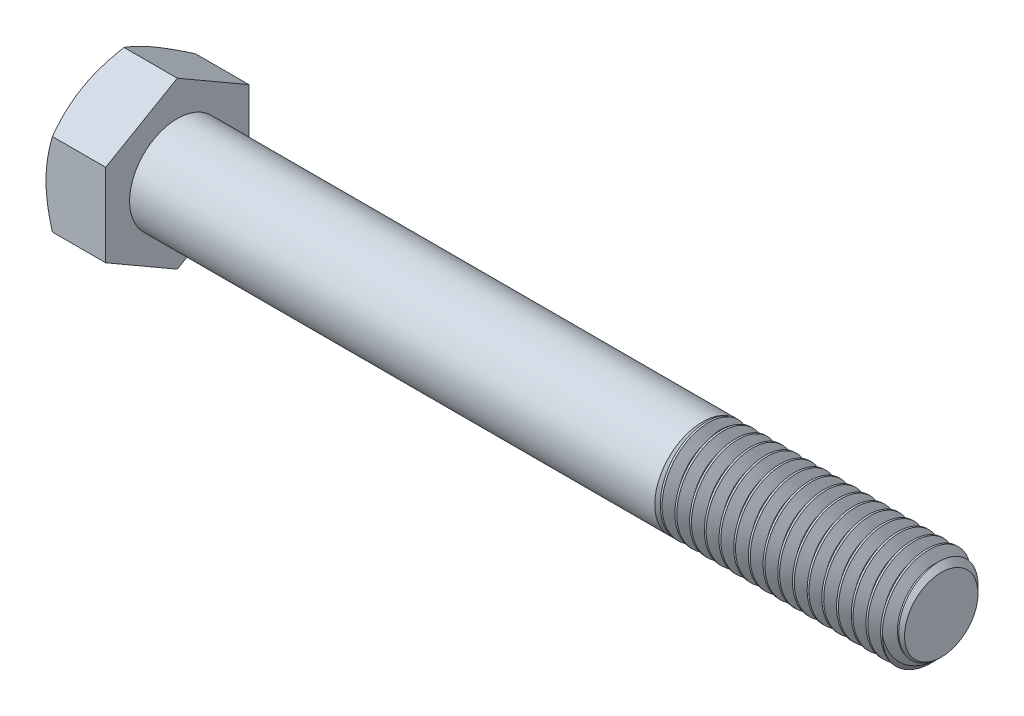
SolidWorks part; units mm, degrees
material "Plain Carbon Steel"
ref_plane "Front Plane" through (0, 0, 0) normal (0, 0, 1) x (1, 0, 0)
ref_plane "Top Plane" through (0, 0, 0) normal (0, 1, 0) x (1, 0, 0)
ref_plane "Right Plane" through (0, 0, 0) normal (1, 0, 0) x (0, 0, -1)
sketch "Sketch1" plane through (0, 0, 0) normal (0, 0, 1) x (1, 0, 0)
  line L0 (-54.7687, 0) -> (54.7687, 0) construction
  line L1 (54.7687, 6.35) -> (54.7687, -6.35) construction
  line L2 (-46.8312, 9.525) -> (-46.8312, -9.525) construction
  line L3 (-54.7687, 9.525) -> (-54.7687, -9.525) construction
  point P9 (-46.8312, 0)
  point P10 (47.9303, -6.35)
  dimension "Screw Dia" = 12.7
  dimension "Hex" = 19.05
  dimension "Head Ht" = 7.9375
  dimension "Screw Lenght" = 101.6
  dimension "D1" = 6.8385
ref_plane "Plane2" through (54.7687, 0, 0) normal (1, 0, 0) x (0, 0, -1)
sketch "Sketch5" plane through (54.7687, 0, 0) normal (1, 0, 0) x (0, 0, -1)
  circle A0 centre (0, 0) radius 6.35
extrude "Boss-Extrude3" add sketch "Sketch5" against normal up to vertex (101.6 mm away) up to point (-46.8312, 0, 0)
sketch "Sketch9" plane through (54.7687, 0, 0) normal (1, 0, 0) x (0, 0, -1)
  circle A1 centre (0, 0) radius 6.35
  circle A2 centre (0, 0) radius 6.35
  dimension "D1" = 0
curve "Helix/Spiral1" pitch 1.9538 height 33.7038 turns 17.25 parameters "Pitch"=1.9538
chamfer "Chamfer1" distance 1.4654 angle 45 1 edges at (54.7687, 0, -6.35)
sketch "Sketch10" plane through (0, 0, 0) normal (0, 0, 1) x (1, 0, 0)
  line L0 (54.7687, 6.35) -> (55.5014, 5.0809)
  line L1 (55.5014, 5.0809) -> (55.7457, 5.0809)
  line L2 (55.7457, 5.0809) -> (56.4784, 6.35)
  line L3 (54.7687, 6.35) -> (56.4784, 6.35)
  line L4 (55.6236, 6.35) -> (55.6236, 5.0809) construction
  line L5 (55.1351, 5.7155) -> (56.112, 5.7155) construction
  dimension "D1" = 60
  dimension "D2" = 0.2442
  dimension "D3" = 0.9769
sweep "Cut-Sweep1" cut profiles "Sketch10" path "Helix/Spiral1" align with end faces yes
sketch "Sketch11" plane through (0, 0, 0) normal (0, 0, 1) x (1, 0, 0)
  line L0 (-46.8312, 6.35) -> (-46.8312, 0)
  line L1 (-46.8312, 0) -> (29.3688, 0)
  line L3 (29.3688, 0) -> (23.0187, 6.35)
  line L4 (-46.8312, 6.35) -> (23.0187, 6.35)
  dimension "D1" = 45
  dimension "MIn Thread" = 31.75
revolve "Revolve1" add sketch "Sketch11" angle 360 about L1
sketch "Sketch6" plane through (-46.8312, 0, 0) normal (-1, 0, 0) x (0, 0, 1)
  line L0 (0, 9.525) -> (0, -9.525) construction
  line L1 (9.525, 5.4993) -> (0, 10.9985)
  line L2 (0, 10.9985) -> (-9.525, 5.4993)
  line L3 (-9.525, 5.4993) -> (-9.525, -5.4993)
  line L4 (-9.525, -5.4993) -> (0, -10.9985)
  line L5 (0, -10.9985) -> (9.525, -5.4993)
  line L6 (9.525, -5.4993) -> (9.525, 5.4993)
  circle A0 centre (0, 0) radius 9.525 construction
extrude "Boss-Extrude4" add sketch "Sketch6" along normal up to vertex
sketch "Sketch7" plane through (-54.7687, 0, 0) normal (-1, 0, 0) x (0, 0, 1)
  circle A0 centre (0, 0) radius 9.525 construction
  circle A1 centre (0, 0) radius 9.525
sketch "Sketch8" plane through (-54.7687, 0, 0) normal (-1, 0, 0) x (0, 0, 1)
  circle A0 centre (0, 0) radius 9.525 construction
  circle A1 centre (0, 0) radius 9.525
extrude "Cut-Extrude3" cut sketch "Sketch8" against normal through all draft 60 flip side to cut
sketch "Sketch12" plane through (-54.7687, 0, 0) normal (-1, 0, 0) x (0, 0, 1)
  line L0 (0, 7.3343) -> (0, 4.0958) construction
  line L1 (0.2858, 7.3343) -> (0.2858, 4.0958)
  line L2 (-0.2858, 7.3343) -> (-0.2857, 4.0958)
  line L3 (0, 6.35) -> (0, -6.35) construction
  arc A0 (0.2858, 7.3343) -> (-0.2858, 7.3343) centre (0, 7.3343) ccw
  arc A1 (-0.2857, 4.0958) -> (0.2858, 4.0958) centre (0, 4.0958) ccw
  circle A3 centre (0, 0) radius 3.81 construction
  circle A4 centre (0, 0) radius 7.62 construction
  point P2 (0, 5.715)
  dimension "D1" = 7.62
  dimension "D3" = 15.24
  dimension "D2" = 0.5715
extrude "Cut-Extrude4" cut sketch "Sketch12" against normal blind 0.254
pattern_circular "CirPattern1" count 3 over 360 about axis through (0, 0, 0) along (1, 0, 0) of "Cut-Extrude4"
equation "\"D2@Sketch10\" = \"Pitch@Helix/Spiral1\"*.125"
equation "\"D3@Sketch10\" = \"Pitch@Helix/Spiral1\"*.5"
equation "\"D3@Helix/Spiral1\" = \"MIn Thread@Sketch11\"+\"Pitch@Helix/Spiral1\""
equation "\"D1@Chamfer1\" = \"Pitch@Helix/Spiral1\"*.75"
equation "\"D1@Sketch12\" = \"Hex@Sketch1\"*.4"
equation "\"D3@Sketch12\" = \"Hex@Sketch1\"*.8"
equation "\"D2@Sketch12\" = \"Hex@Sketch1\"*.03"
equation "\"D1@Sketch1\" = \"Pitch@Helix/Spiral1\"*3.5"
